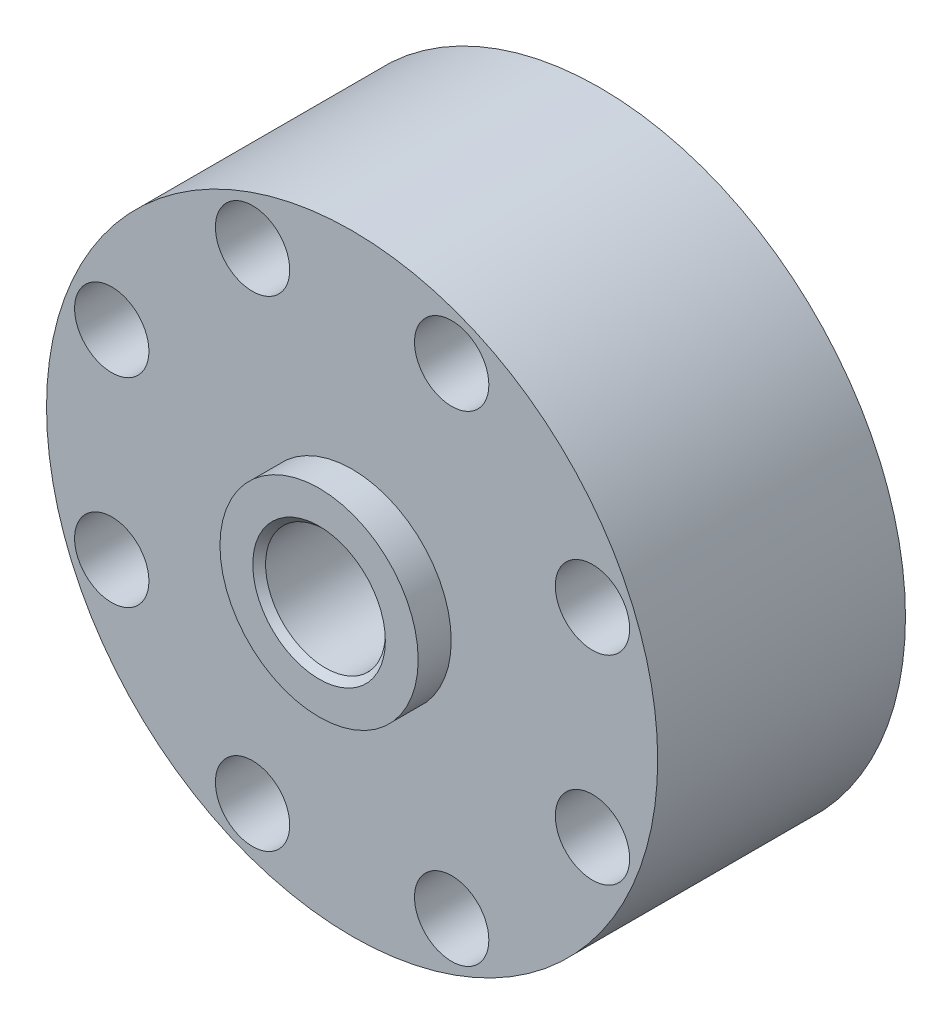
SolidWorks part; units mm, degrees
material "AISI 304"
ref_plane "Plano frontal" through (0, 0, 0) normal (0, 0, 1) x (1, 0, 0)
ref_plane "Plano superior" through (0, 0, 0) normal (0, 1, 0) x (1, 0, 0)
ref_plane "Plano direito" through (0, 0, 0) normal (1, 0, 0) x (0, 0, -1)
sketch "Esboço1" plane through (0, 0, 0) normal (0, 0, 1) x (1, 0, 0)
  circle A0 centre (0, 0) radius 37
  dimension "D1" = 74
extrude "Ressalto-extrusão1" add sketch "Esboço1" along normal blind 30
sketch "Esboço2" plane through (0, 0, 30) normal (0, 0, 1) x (1, 0, 0)
  line L0 (0, 0) -> (0, 31.5) construction
  line L1 (0, 0) -> (-12.0545, 29.1022) construction
  circle A0 centre (0, 0) radius 31.5 construction
  circle A1 centre (-12.0545, 29.1022) radius 3 construction
  dimension "D1" = 63
  dimension "D2" = 6
  dimension "D3" = 22.5
hole_wizard "Furo1" positions "3DSketch1" profile "Esboço3" legacy end condition through all
sketch3d "3DSketch1"
  point P0 (-12.0545, 29.1022, 30)
sketch "Esboço3" plane through (-12.0545, 29.1022, 30) normal (1, 0, 0) x (0, -1, 0)
  line L0 (0, 0) -> (0, 30)
  line L1 (0, 30) -> (3, 30)
  line L2 (3, 30) -> (3, 7)
  line L3 (3, 7) -> (4.5, 7)
  line L4 (4.5, 7) -> (4.5, 0)
  line L5 (4.5, 0) -> (0, 0)
  line L6 (0, 110) -> (0, -10) construction
  dimension "Diameter" = 6
  dimension "Depth" = 30
  dimension "C-Bore Diameter" = 9
  dimension "C-Bore Depth" = 7
ref_axis "Eixo1" through (0, 0, 30) along (0, 0, 1)
pattern_circular "PadrãoCircular1" count 8 over 360 about axis through (0, 0, 30) along (0, 0, 1) of "Furo1"
sketch "Esboço4" plane through (0, 0, 30) normal (0, 0, 1) x (1, 0, 0)
  circle A0 centre (0, 0) radius 12
  dimension "D1" = 24
extrude "Ressalto-extrusão2" add sketch "Esboço4" along normal blind 4
hole_wizard "Furo roscado de M16x1.51" positions "Esboço6" profile "Esboço7" tap size "M16x1.5" standard "ISO" end condition through all
sketch "Esboço6" plane through (0, 0, 34) normal (0, 0, 1) x (1, 0, 0)
  point P0 (0, 0)
sketch "Esboço7" plane through (0, 0, 34) normal (1, 0, 0) x (0, -1, 0)
  line L0 (0, 0) -> (0, 34)
  line L1 (0, 34) -> (8.025, 34)
  line L2 (7.25, 33.225) -> (7.25, 0.775)
  line L3 (7.25, 0.775) -> (8.025, 0)
  line L5 (8.025, 0) -> (0, 0)
  line L6 (-7.25, 0.775) -> (-8.025, 0) construction
  line L7 (8.025, 34) -> (7.25, 33.225)
  line L8 (-8.025, 34) -> (-7.25, 33.225) construction
  line L11 (0, -6.35) -> (0, 107.95) construction
  dimension "Thru Tap Drill Dia." = 14.5
  dimension "Thru Tap Drill Depth" = 34
  dimension "Near C'Sink Dia." = 16.05
  dimension "Near C'Sink Angle" = 90
  dimension "Far C'Sink Dia." = 16.05
  dimension "Far C'Sink Angle" = 90
cosmetic thread "Rosca de furo1" parameters "D2"=16
